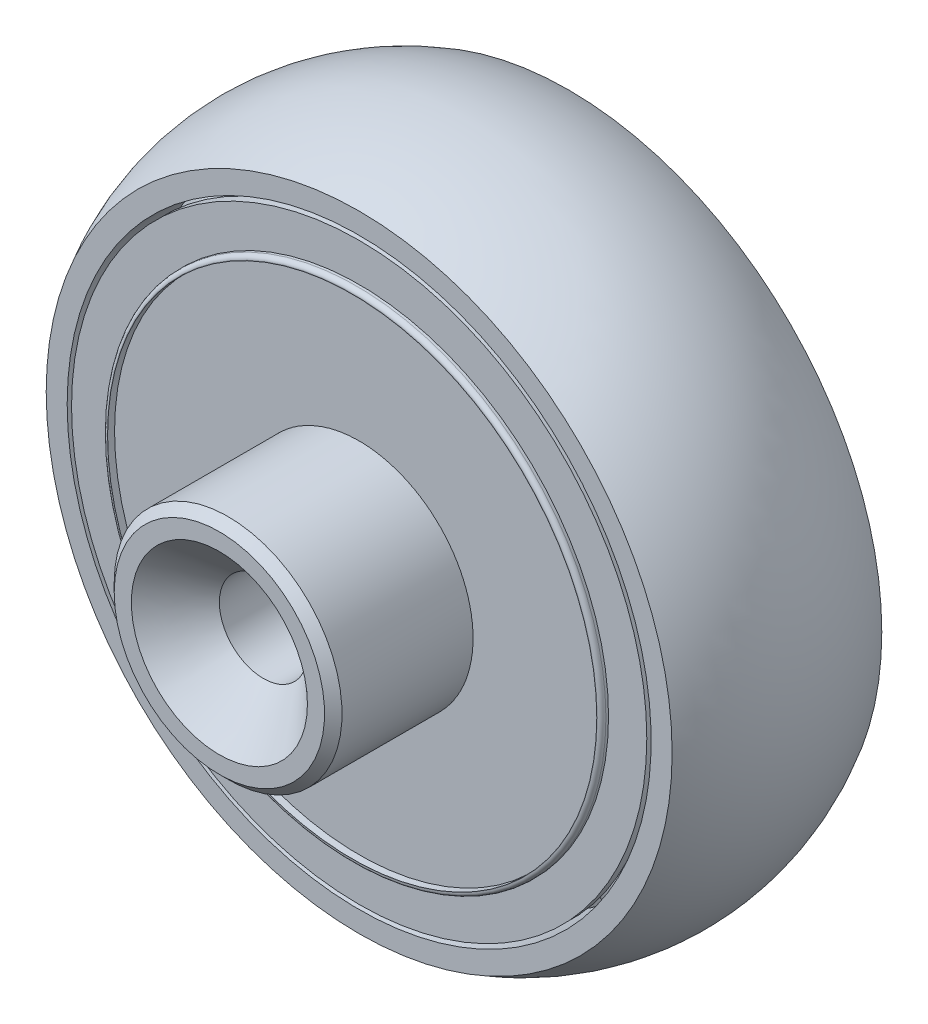
SolidWorks part; units mm, degrees
ref_plane "Front Plane" through (0, 0, 0) normal (0, 0, 1) x (1, 0, 0)
ref_plane "Top Plane" through (0, 0, 0) normal (0, 1, 0) x (1, 0, 0)
ref_plane "Right Plane" through (0, 0, 0) normal (1, 0, 0) x (0, 0, -1)
sketch "Sketch2" plane through (0, 0, 0) normal (1, 0, 0) x (0, 0, -1)
  line L0 (65.1655, 0) -> (0, 0) construction
  line L1 (0, 0) -> (0, 54.9666) construction
  line L2 (3.583, 26.5308) -> (9.525, 26.5308)
  line L3 (-9.525, 28.4358) -> (9.525, 28.4358) construction
  line L4 (-9.525, 28.4358) -> (-9.525, 26.5308)
  line L5 (-9.525, 26.5308) -> (-3.583, 26.5308)
  line L6 (9.525, 28.4358) -> (9.525, 26.5308)
  line L7 (-9.525, 28.4358) -> (9.525, 26.5308) construction
  line L8 (-9.525, 26.5308) -> (9.525, 28.4358) construction
  arc A0 (3.583, 26.5308) -> (-3.583, 26.5308) centre (0, 25.2354) ccw
  arc A1 (-9.525, 28.4358) -> (9.525, 28.4358) centre (0, 11.938) cw
  point P4 (0, 27.4833)
  dimension "D4" = 7.62
  dimension "D6" = 19.05
  dimension "D1" = 1.905
  dimension "D2" = 9.525
  dimension "D3" = 28.4358
  dimension "D5" = 1.2954
revolve "Revolve1" add sketch "Sketch2" angle 360 about L0
sketch "Sketch3" plane through (0, 0, 0) normal (1, 0, 0) x (0, 0, -1)
  line L0 (25.7703, 0) -> (0, 0) construction
  line L1 (0, 0) -> (0, -35.5483) construction
  line L2 (4.207, -25.2354) -> (-4.207, -25.2354)
  arc A1 (-4.207, -25.2354) -> (4.207, -25.2354) centre (0, -25.2354) ccw
  arc A2 (-3.583, -26.5308) -> (3.583, -26.5308) centre (0, -25.2354) ccw construction
  dimension "D1" = 0.397
revolve "Revolve2" add sketch "Sketch3" angle 360 about L2
pattern_circular "CirPattern1" count 17 over 360 about axis through (0, 0, 3.583) along (0, 0, -1) of "Revolve2"
ref_axis "Axis1" through (0, 0, -10.4775) along (0, 0, 1)
sketch "Sketch4" plane through (0, 0, 0) normal (1, 0, 0) x (0, 0, -1)
  line L0 (0, 0) -> (0, 29.1886) construction
  line L1 (10.4775, 0) -> (-10.4775, 0) construction
  line L2 (15.875, 10.35) -> (-22.225, 10.35)
  line L3 (15.875, 10.35) -> (15.875, 4)
  line L4 (15.875, 4) -> (-22.225, 4)
  line L5 (-22.225, 10.35) -> (-22.225, 4)
  line L6 (9.525, -28.4358) -> (9.525, 28.4358) construction
  line L7 (-9.525, 28.4358) -> (-9.525, -28.4358) construction
  dimension "D1" = 4
  dimension "D2" = 6.35
  dimension "D3" = 6.35
  dimension "D4" = 12.7
revolve "Revolve3" add sketch "Sketch4" angle 360 about axis through (0, 0, -10.4775) along (0, 0, 1)
chamfer "Chamfer1" distance 4 angle 45 2 edges at (-4, 0, 22.225) (-4, 0, -15.875)
chamfer "Chamfer2" distance 0.7937 angle 45 2 edges at (-10.35, 0, -15.875) (-10.35, 0, 22.225)
sketch "Sketch6" plane through (0, 0, 9.525) normal (0, 0, 1) x (1, 0, 0)
  circle A0 centre (0, 0) radius 10.35 construction
  circle A1 centre (0, 0) radius 10.35
  circle A2 centre (0, 0) radius 26.1338
  circle A3 centre (0, 0) radius 26.5308 construction
  dimension "D1" = 0.397
extrude "Boss-Extrude1" add sketch "Sketch6" against normal blind 0.7937
sketch "Sketch7" plane through (0, 0, 9.525) normal (0, 0, 1) x (1, 0, 0)
  circle A0 centre (0, 0) radius 22.225 construction
  circle A1 centre (0, 0) radius 22.225
  circle A2 centre (0, 0) radius 22.6568
  dimension "D1" = 0.4318
extrude "Boss-Extrude2" add sketch "Sketch7" along normal blind 0.635
fillet "Fillet1" radius 0.397 1 edges at (22.6568, 0, 10.16)
mirror "Mirror2" about plane through (0, 0, 0) normal (0, 0, 1) rebuild error yes
equation "\"in\"=0.0625"
